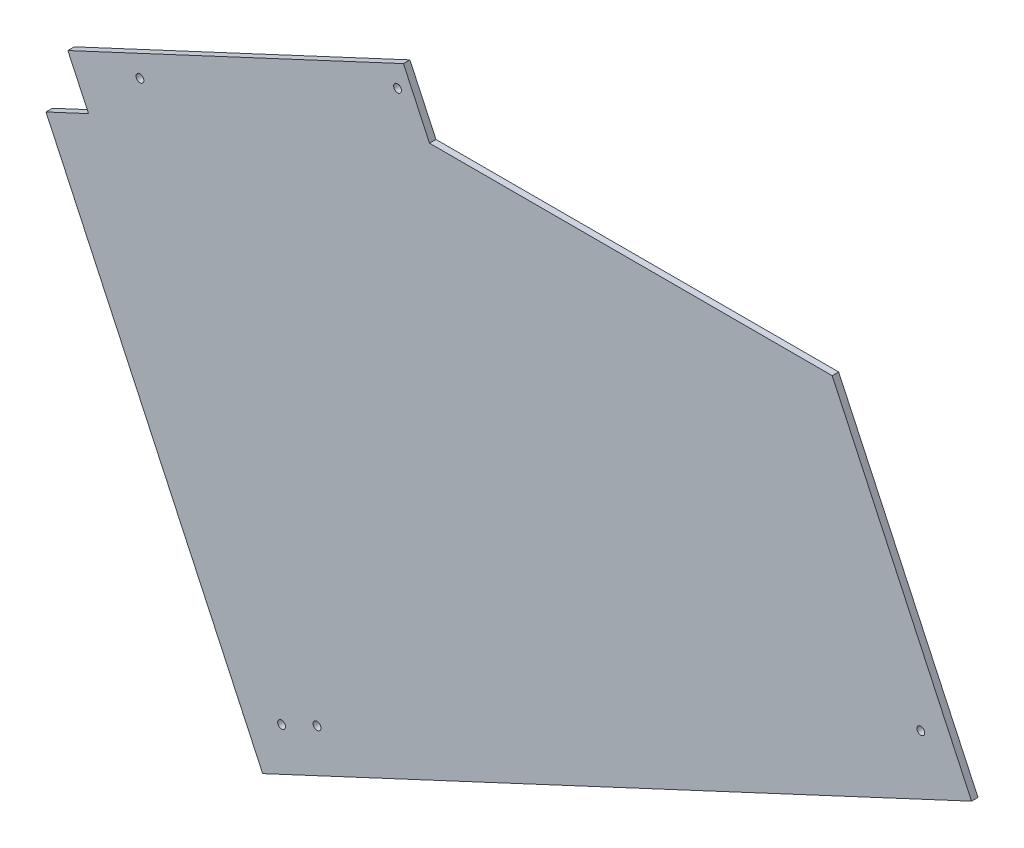
SolidWorks part; units mm, degrees
ref_plane "Front Plane" through (0, 0, 0) normal (0, 0, 1) x (1, 0, 0)
ref_plane "Top Plane" through (0, 0, 0) normal (0, 1, 0) x (1, 0, 0)
ref_plane "Right Plane" through (0, 0, 0) normal (1, 0, 0) x (0, 0, -1)
sketch "Sketch1" plane through (0, 0, 0) normal (0, 0, 1) x (1, 0, 0)
  line L0 (327.4362, 0.0035) -> (121.4984, 0.0035)
  line L1 (121.4984, 0.0035) -> (108.169, 28.5884)
  line L2 (108.169, 28.5884) -> (-63.4467, -51.4373)
  line L3 (-63.4467, -51.4373) -> (57.9293, -311.7289) construction
  line L4 (57.9293, -311.7289) -> (398.701, -152.8244)
  line L5 (271.5352, 119.8836) -> (277.3251, 107.4672) construction
  line L6 (190.5834, 136.311) -> (-12.0446, 41.824) construction
  line L7 (-63.4467, -51.4373) -> (255.5737, 97.3243) construction
  line L8 (398.701, -152.8244) -> (327.4362, 0.0035)
  line L9 (57.9293, -311.7289) -> (36.1779, -321.8717)
  line L10 (36.1779, -321.8717) -> (-74.6326, -84.2378)
  line L11 (50.7481, 0) -> (323.7481, 0) construction
  line L12 (-74.6326, -84.2378) -> (-52.8812, -74.095)
  line L13 (-90.9879, -49.1637) -> (-85.1981, -61.5801) construction
  line L14 (-52.8812, -74.095) -> (-63.4467, -51.4373)
  circle A0 centre (162.7613, -40.6644) radius 32.5 construction
  circle A1 centre (336.0773, -108.8767) radius 32.5 construction
  circle A2 centre (90.1802, -40.6644) radius 32.5 construction
  circle A3 centre (232.5481, -40.6644) radius 32.5 construction
  circle A4 centre (207.2768, 100.5118) radius 39.5 construction
  arc A5 (-3.3339, 41.4724) -> (-17.3744, 34.9252) centre (-8.0297, 33.2141) ccw construction
  circle A6 centre (304.5287, -40.6644) radius 32.5 construction
  circle A7 centre (254.9584, -108.8767) radius 32.5 construction
  circle A8 centre (179.3206, -108.8767) radius 32.5 construction
  circle A9 centre (101.4264, -108.8767) radius 32.5 construction
  circle A10 centre (270.383, -163.8108) radius 32.5 construction
  circle A11 centre (372.7594, -134.5783) radius 2
  dimension "D2" = 65
  dimension "D3" = 65
  dimension "D5" = 4
  dimension "D1" = 350
  dimension "D4" = 25
  dimension "24.5/2" = 15.8
  dimension "D6" = 27.5
extrude "Boss-Extrude1" add sketch "Sketch1" along normal up to surface (3.3 mm away)
sketch "Sketch2" plane through (0, 0, 3.3) normal (0, 0, 1) x (1, 0, 0)
  circle A0 centre (105.1447, 16.1444) radius 2
  circle A1 centre (-26.5934, -45.2861) radius 2
  circle A2 centre (-26.5934, -45.2861) radius 2 construction
  circle A3 centre (105.1447, 16.1444) radius 2 construction
extrude "Cut-Extrude1" cut sketch "Sketch2" against normal through all
sketch "Sketch3" plane through (0, 0, 3.3) normal (0, 0, 1) x (1, 0, 0)
  line L2 (398.701, -152.8244) -> (36.1779, -321.8717) construction
  line L3 (36.1779, -321.8717) -> (-74.6326, -84.2378) construction
  circle A0 centre (45.8517, -295.2932) radius 2
  circle A1 centre (63.9779, -286.8408) radius 2
  point P6 (0, 0)
  point P9 (0, 0)
  dimension "D1" = 4
  dimension "D2" = 4
  dimension "D3" = 20
  dimension "D5" = 20
  dimension "D6" = 20
  dimension "D4" = 20
extrude "Cut-Extrude2" cut sketch "Sketch3" against normal blind 4
